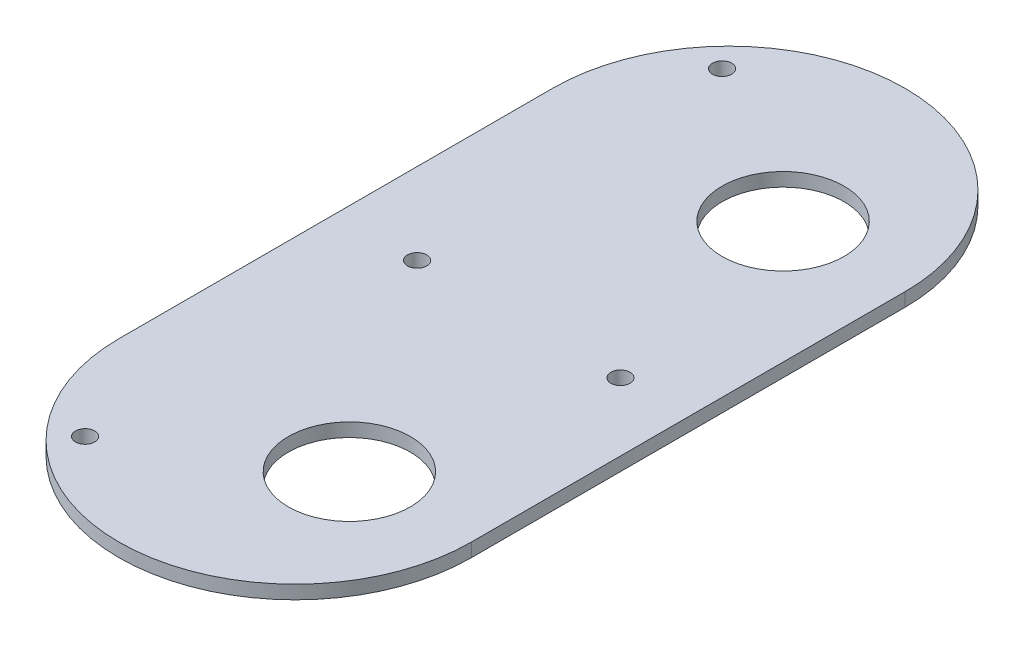
SolidWorks part; units mm, degrees
material "6061-T6 (SS)"
ref_plane "Front" through (0, 0, 0) normal (0, 0, 1) x (1, 0, 0)
ref_plane "Top" through (0, 0, 0) normal (0, 1, 0) x (1, 0, 0)
ref_plane "Right" through (0, 0, 0) normal (1, 0, 0) x (0, 0, -1)
sketch "Sketch1" plane through (0, 0, 0) normal (0, 1, 0) x (1, 0, 0)
  line L0 (0, 50.8) -> (0, -50.8) construction
  line L1 (-53.9705, 50.8) -> (-53.9705, -50.8)
  line L2 (28.5705, 50.8) -> (28.5705, -50.8)
  circle A0 centre (0, 50.8) radius 14.2875
  circle A1 centre (0, -50.8) radius 14.2875
  circle A4 centre (0, 50.8) radius 38.1 construction
  circle A5 centre (0, -50.8) radius 38.1 construction
  arc A6 (-53.9705, -50.8) -> (28.5705, -50.8) centre (-12.7, -50.8) ccw
  arc A7 (-53.9705, 50.8) -> (28.5705, 50.8) centre (-12.7, 50.8) cw
  point P4 (0, 0)
  dimension "D2" = 28.575
  dimension "D3" = 41.2705
  dimension "D4" = 76.2
  dimension "D1" = 101.6
  dimension "D5" = 12.7
extrude "Boss-Extrude1" add sketch "Sketch1" along normal blind 3.175
hole_wizard "#8 Clearance Hole1" positions "Sketch2" profile "Sketch3" hole size "#8" standard "ANSI Inch"
sketch "Sketch2" plane through (0, 3.175, 0) normal (0, 1, 0) x (1, 0, 0)
  line L6 (0, 50.8) -> (0, -50.8) construction
  line L9 (-38.1, 74.6125) -> (-38.1, -74.6125) construction
  point P2 (12.7, 0)
  point P4 (-38.1, 74.6125)
  point P10 (-38.1, -74.6125)
  point P40 (-34.925, 0)
  point P51 (-38.1, 0)
  point P53 (0, 0)
  point P54 (0, 0)
  point P55 (-38.1, 75.5513)
  dimension "D1" = 12.7
  dimension "D2" = 34.925
  dimension "D3" = 38.1
  dimension "D4" = 149.225
sketch "Sketch3" plane through (12.7, 3.175, 0) normal (1, 0, 0) x (0, 0, 1)
  line L0 (0, 0) -> (0, 4.5257)
  line L1 (0, 4.5257) -> (2.2479, 3.175)
  line L2 (2.2479, 3.175) -> (2.2479, 0)
  line L5 (2.2479, 0) -> (0, 0)
  line L10 (0, 4.5257) -> (-2.2479, 3.175) construction
  line L11 (0, -6.35) -> (0, 107.95) construction
  dimension "Hole Dia." = 4.4958
  dimension "Hole Depth" = 3.175
  dimension "Drill Angle" = 118
